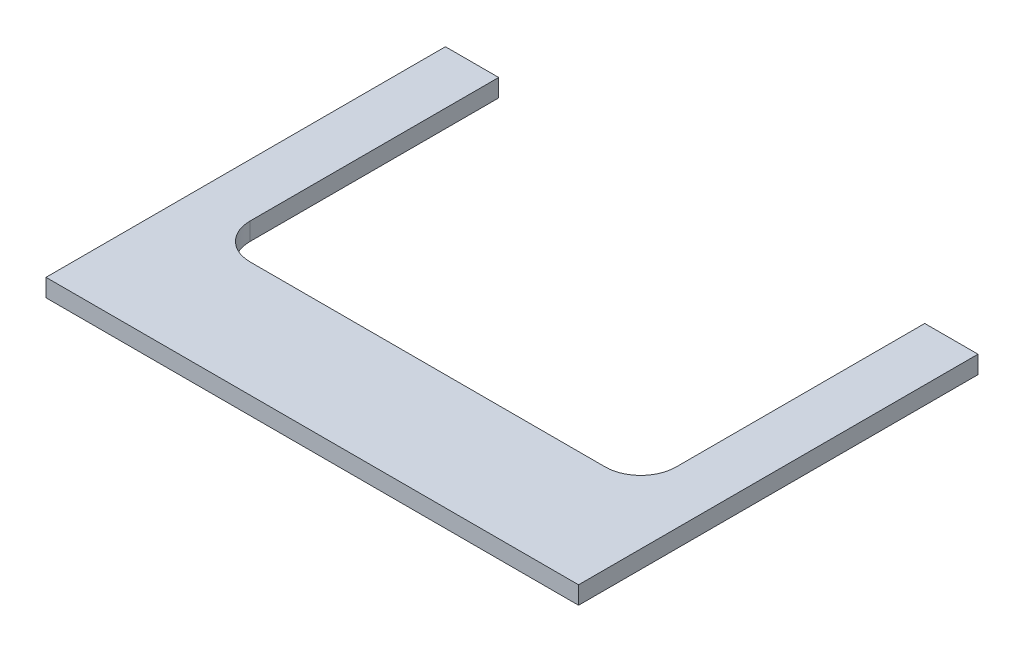
SolidWorks part; units mm, degrees
ref_plane "前视基准面" through (0, 0, 0) normal (0, 0, 1) x (1, 0, 0)
ref_plane "上视基准面" through (0, 0, 0) normal (0, 1, 0) x (1, 0, 0)
ref_plane "右视基准面" through (0, 0, 0) normal (1, 0, 0) x (0, 0, -1)
sketch "草图1" plane through (0, 0, 0) normal (0, 1, 0) x (1, 0, 0)
  line L1 (-120, 32.5) -> (120, 32.5)
  line L2 (-150, 192.5) -> (-120, 192.5)
  line L3 (-150, 192.5) -> (-150, 32.5)
  line L5 (-150, 32.5) -> (150, -32.5) construction
  line L6 (-150, -32.5) -> (150, 32.5) construction
  line L7 (-150, 32.5) -> (-150, -32.5)
  line L8 (-120, 192.5) -> (-120, 32.5)
  line L9 (150, 32.5) -> (150, 192.5)
  line L10 (150, 192.5) -> (120, 192.5)
  line L11 (-150, -32.5) -> (150, -32.5)
  line L12 (150, 32.5) -> (150, -32.5)
  line L13 (120, 32.5) -> (120, 192.5)
  point P0 (0, 0)
  dimension "D1" = 300
  dimension "D2" = 240
  dimension "D3" = 160
  dimension "D4" = 65
extrude "凸台-拉伸1" add sketch "草图1" along normal blind 10
fillet "圆角7" radius 20 2 edges at (120, 5, -32.5) (-120, 5, -32.5)
